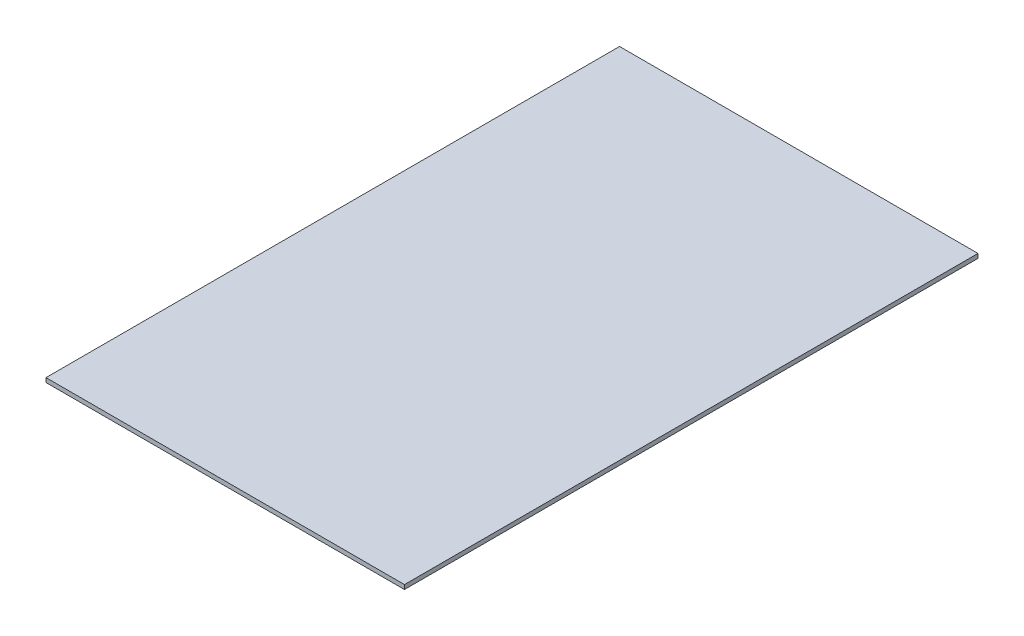
SolidWorks part; units mm, degrees
ref_plane "Front Plane" through (0, 0, 0) normal (0, 0, 1) x (1, 0, 0)
ref_plane "Top Plane" through (0, 0, 0) normal (0, 1, 0) x (1, 0, 0)
ref_plane "Right Plane" through (0, 0, 0) normal (1, 0, 0) x (0, 0, -1)
sketch "Sketch2" plane through (0, 0, 0) normal (0, 1, 0) x (1, 0, 0)
  line L1 (0, 0) -> (250, 0)
  line L2 (0, 0) -> (0, 400)
  line L3 (0, 400) -> (250, 400)
  line L4 (250, 0) -> (250, 400)
  dimension "D1" = 400
  dimension "D2" = 250
extrude "Boss-Extrude1" add sketch "Sketch2" along normal blind 3
